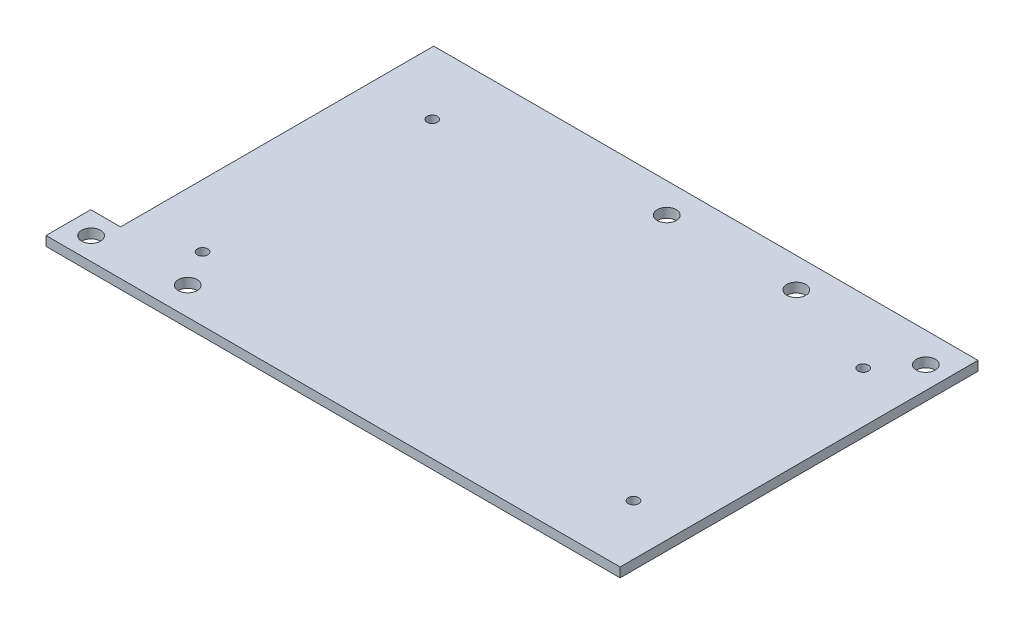
SolidWorks part; units mm, degrees
ref_plane "Front Plane" through (0, 0, 0) normal (0, 0, 1) x (1, 0, 0)
ref_plane "Top Plane" through (0, 0, 0) normal (0, 1, 0) x (1, 0, 0)
ref_plane "Right Plane" through (0, 0, 0) normal (1, 0, 0) x (0, 0, -1)
sketch "Sketch1" plane through (0, 0, 0) normal (0, 1, 0) x (1, 0, 0)
  line L0 (15, -15) -> (39.6804, -15) construction
  line L1 (0, 0) -> (365, 0)
  line L2 (0, 0) -> (0, -210)
  line L3 (-20, -240) -> (365, -240)
  line L4 (365, 0) -> (365, -240)
  line L5 (-4.7537, -225) -> (15.7755, -223.7531) construction
  line L6 (176.2667, -20) -> (263.1333, -20) construction
  line L8 (42, -43) -> (42, -197) construction
  line L9 (42, -197) -> (331, -197) construction
  line L10 (331, -197) -> (331, -43) construction
  line L11 (331, -43) -> (42, -43) construction
  line L12 (42, -43) -> (34, -43) construction
  line L13 (331, -43) -> (331, -35) construction
  line L14 (331, -197) -> (331, -205) construction
  line L15 (263.1333, -20) -> (350, -20) construction
  line L16 (176.2667, -20) -> (263.1333, -20) construction
  line L17 (0, -210) -> (-20, -210)
  line L18 (-20, -210) -> (-20, -240)
  line L19 (0, -210) -> (0, -240) construction
  line L20 (36.8653, -240) -> (35.1476, -211.7207) construction
  line L22 (44.6629, -368.3803) -> (19.543, 45.1949) construction
  line L23 (16.7623, -240) -> (15.1389, -213.2731) construction
  line L24 (-0.4861, 43.9784) -> (24.6338, -369.5969) construction
  line L25 (35.8046, -222.5366) -> (56.3337, -221.2896) construction
  line L26 (15.7755, -223.7531) -> (35.8046, -222.5366) construction
  circle A2 centre (-4.7537, -225) radius 6.35
  circle A3 centre (56.3337, -221.2896) radius 6.35
  circle A8 centre (42, -43) radius 3.5
  circle A9 centre (42, -197) radius 3.5
  circle A10 centre (331, -197) radius 3.5
  circle A11 centre (331, -43) radius 3.5
  circle A12 centre (263.1333, -20) radius 6.35
  circle A19 centre (176.2667, -20) radius 6.35
  circle A20 centre (350, -20) radius 6.35
  circle A21 centre (176.2667, -20) radius 6.35 construction
  circle A22 centre (350, -20) radius 6.35 construction
  circle A23 centre (176.2667, -20) radius 6.35 construction
  circle A24 centre (350, -20) radius 6.35 construction
  point P10 (331, -120)
  point P11 (365, -120)
  point P46 (215.7924, -230.8574)
  point P52 (228.9174, -351.8763)
  dimension "D10" = 7
  dimension "D19" = 12.7
  dimension "D2" = 365
  dimension "D3" = 15
  dimension "D4" = 15
  dimension "D5" = 15
  dimension "D6" = 61.2
  dimension "D7" = 240
  dimension "D8" = 15
  dimension "D9" = 20
  dimension "D11" = 289
  dimension "D12" = 154
  dimension "D13" = 8
  dimension "D14" = 34
  dimension "D15" = 8
  dimension "D16" = 20
  dimension "D17" = 8
  dimension "D18" = 30
extrude "Boss-Extrude1" add sketch "Sketch1" against normal blind 6.35
